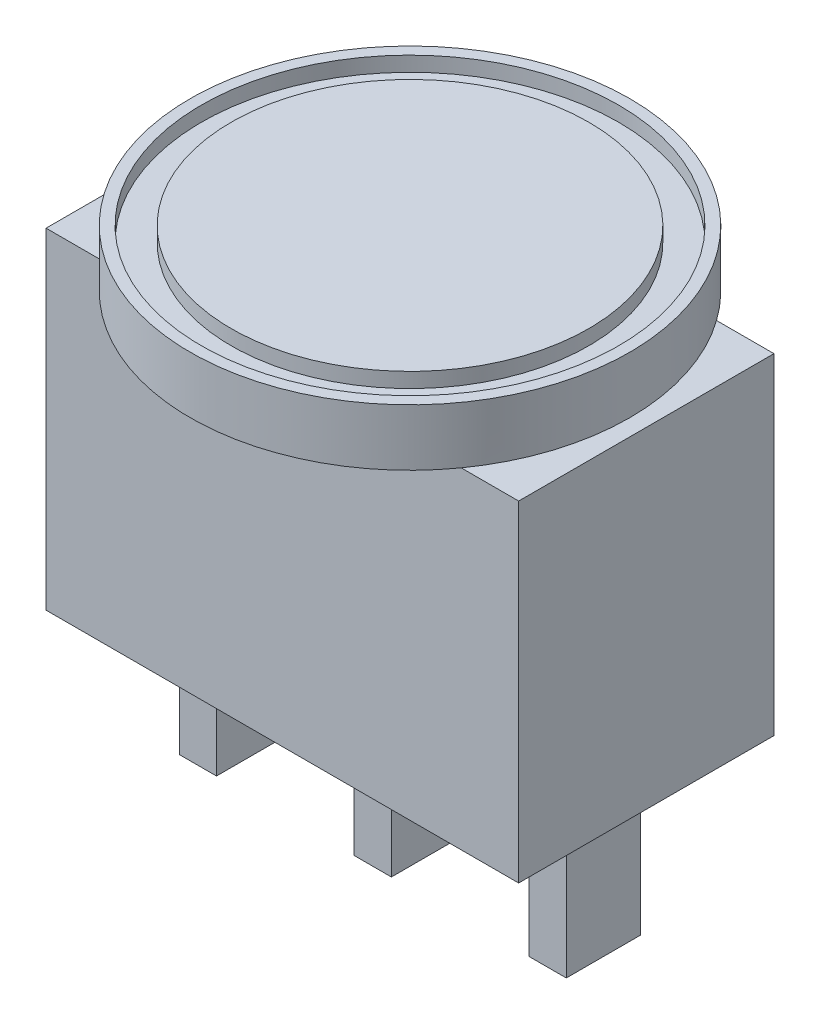
SolidWorks part; units mm, degrees
ref_plane "Front Plane" through (0, 0, 0) normal (0, 0, 1) x (1, 0, 0)
ref_plane "Top Plane" through (0, 0, 0) normal (0, 1, 0) x (1, 0, 0)
ref_plane "Right Plane" through (0, 0, 0) normal (1, 0, 0) x (0, 0, -1)
sketch "Sketch1" plane through (0, 0, 0) normal (0, 0, 1) x (1, 0, 0)
  line L1 (-6.35, -8.89) -> (6.35, -8.89)
  line L2 (-6.35, -8.89) -> (-6.35, 0)
  line L3 (-6.35, 0) -> (6.35, 0)
  line L4 (6.35, -8.89) -> (6.35, 0)
  point P4 (0, 0)
  dimension "D1" = 12.7
  dimension "D2" = 8.89
extrude "Boss-Extrude1" add sketch "Sketch1" along normal blind 3.43 and the other way blind 3.43
sketch "Sketch2" plane through (0, 0, 0) normal (0, 0, 1) x (1, 0, 0)
  line L0 (-6.35, -8.89) -> (6.35, -8.89) construction
  line L1 (-5.2, -8.89) -> (-4.2, -8.89)
  line L2 (-5.2, -8.89) -> (-5.2, -12.89)
  line L3 (-5.2, -12.89) -> (-4.2, -12.89)
  line L4 (-4.2, -8.89) -> (-4.2, -12.89)
  line L5 (0.5, -8.89) -> (0.5, -12.89)
  line L6 (-0.5, -12.89) -> (0.5, -12.89)
  line L7 (-0.5, -8.89) -> (-0.5, -12.89)
  line L8 (-0.5, -8.89) -> (0.5, -8.89)
  line L9 (5.2, -8.89) -> (5.2, -12.89)
  line L10 (4.2, -12.89) -> (5.2, -12.89)
  line L11 (4.2, -8.89) -> (4.2, -12.89)
  line L12 (4.2, -8.89) -> (5.2, -8.89)
  point P7 (0, -8.89)
  dimension "D1" = 4
  dimension "D2" = 1
  dimension "D4" = 4.7
  dimension "D3" = 3
extrude "Boss-Extrude2" add sketch "Sketch2" along normal blind 1 and the other way blind 1
sketch "Sketch3" plane through (0, 0, 0) normal (0, 0, 1) x (1, 0, 0)
  line L0 (0, 0) -> (0, 1.524)
  line L1 (0, 1.524) -> (4.805, 1.524)
  line L2 (4.805, 1.524) -> (4.805, 1.124)
  line L3 (4.805, 1.124) -> (5.605, 1.124)
  line L4 (5.605, 1.124) -> (5.605, 1.524)
  line L5 (5.605, 1.524) -> (5.905, 1.524)
  line L6 (5.905, 1.524) -> (5.905, 0)
  line L9 (6.35, 0) -> (-6.35, 0) construction
  line L10 (5.905, 0) -> (0, 0)
  point P3 (5.205, 1.124)
  point P10 (5.905, 0)
  point P14 (4.741, 1.524)
  point P15 (5.905, 0.0764)
  dimension "D2" = 1.524
  dimension "D3" = 0.4
  dimension "D4" = 5.905
  dimension "D5" = 0.3
  dimension "D6" = 0.8
revolve "Revolve1" add sketch "Sketch3" angle 360 about L0
